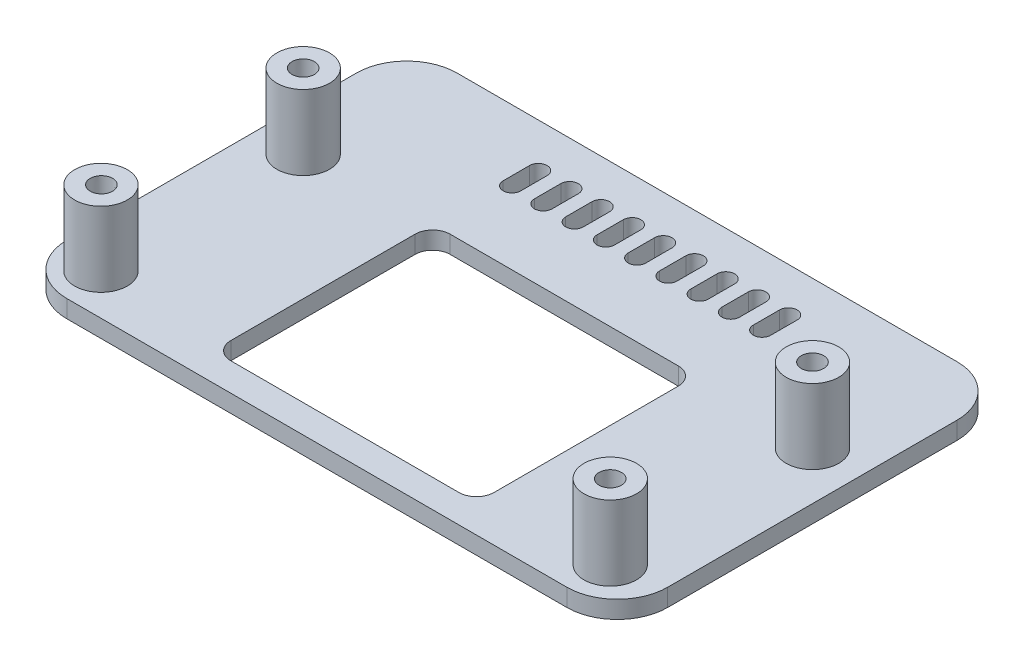
SolidWorks part; units mm, degrees
ref_plane "前视基准面" through (0, 0, 0) normal (0, 0, 1) x (1, 0, 0)
ref_plane "上视基准面" through (0, 0, 0) normal (0, 1, 0) x (1, 0, 0)
ref_plane "右视基准面" through (0, 0, 0) normal (1, 0, 0) x (0, 0, -1)
other "Configuration Table"
sketch "草图1" plane through (0, 0, 0) normal (0, 1, 0) x (1, 0, 0)
  line L1 (-34.4994, 19.3243) -> (34.0006, 19.3243)
  line L2 (-34.4994, 19.3243) -> (-34.4994, -25.1757)
  line L3 (-34.4994, -25.1757) -> (34.0006, -25.1757)
  line L4 (34.0006, 19.3243) -> (34.0006, -25.1757)
  dimension "D1" = 68.5
  dimension "D2" = 44.5
extrude "凸台-拉伸1" add sketch "草图1" along normal blind 2
fillet "圆角1" radius 5.75 4 edges at (34.0006, 1, -19.3243) (34.0006, 1, 25.1757) (-34.4994, 1, 25.1757) (-34.4994, 1, -19.3243)
sketch "草图2" plane through (0, 0, 0) normal (0, -1, 0) x (1, 0, 0)
  line L0 (-28.7494, 25.1757) -> (28.2506, 25.1757) construction
  line L1 (-15.2494, 21.9757) -> (14.7506, 21.9757)
  line L2 (-15.2494, 21.9757) -> (-15.2494, -3.0243)
  line L3 (-15.2494, -3.0243) -> (14.7506, -3.0243)
  line L4 (14.7506, 21.9757) -> (14.7506, -3.0243)
  line L5 (-15.2494, 21.9757) -> (14.7506, -3.0243) construction
  line L6 (-15.2494, -3.0243) -> (14.7506, 21.9757) construction
  point P0 (-0.2494, 9.4757)
  point P8 (-0.2494, 25.1757)
  dimension "D1" = 15.7
  dimension "D2" = 30
  dimension "D3" = 25
extrude "切除-拉伸1" cut sketch "草图2" against normal through all
fillet "圆角2" radius 2 4 edges at (-15.2494, 1, -3.0243) (-15.2494, 1, 21.9757) (14.7506, 1, 21.9757) (14.7506, 1, -3.0243)
sketch "草图3" plane through (0, 2, 0) normal (0, 1, 0) x (1, 0, 0)
  circle A0 centre (-29.5244, 2.5493) radius 3
  circle A1 centre (-29.5244, -20.5007) radius 3
  circle A2 centre (28.5006, -20.4757) radius 3
  circle A3 centre (28.5256, 2.5493) radius 3
  dimension "D1" = 6
extrude "凸台-拉伸2" add sketch "草图3" along normal blind 8.5
sketch "草图4" plane through (0, 10.5, 0) normal (0, 1, 0) x (1, 0, 0)
  circle A0 centre (-29.5244, 2.5493) radius 1.275
  circle A1 centre (-29.4994, -20.4757) radius 1.275
  circle A2 centre (28.5256, -20.5007) radius 1.275
  circle A3 centre (28.5256, 2.5493) radius 1.275
  dimension "D1" = 2.55
extrude "切除-拉伸2" cut sketch "草图4" against normal blind 6 draft 1
sketch "草图5" plane through (0, 0, 0) normal (0, -1, 0) x (1, 0, 0)
  line L0 (-14.4994, -11.3243) -> (-14.4994, -14.3243) construction
  line L1 (-13.4994, -11.3243) -> (-13.4994, -14.3243)
  line L2 (-15.4994, -11.3243) -> (-15.4994, -14.3243)
  line L3 (-10.9369, -11.3243) -> (-10.9369, -14.3243) construction
  line L4 (-9.9369, -11.3243) -> (-9.9369, -14.3243)
  line L5 (-11.9369, -11.3243) -> (-11.9369, -14.3243)
  line L6 (-7.3744, -11.3243) -> (-7.3744, -14.3243) construction
  line L7 (-6.3744, -11.3243) -> (-6.3744, -14.3243)
  line L8 (-8.3744, -11.3243) -> (-8.3744, -14.3243)
  line L9 (-3.8119, -11.3243) -> (-3.8119, -14.3243) construction
  line L10 (-2.8119, -11.3243) -> (-2.8119, -14.3243)
  line L11 (-4.8119, -11.3243) -> (-4.8119, -14.3243)
  line L12 (-0.2494, -11.3243) -> (-0.2494, -14.3243) construction
  line L13 (0.7506, -11.3243) -> (0.7506, -14.3243)
  line L14 (-1.2494, -11.3243) -> (-1.2494, -14.3243)
  line L15 (3.3131, -11.3243) -> (3.3131, -14.3243) construction
  line L16 (4.3131, -11.3243) -> (4.3131, -14.3243)
  line L17 (2.3131, -11.3243) -> (2.3131, -14.3243)
  line L18 (6.8756, -11.3243) -> (6.8756, -14.3243) construction
  line L19 (7.8756, -11.3243) -> (7.8756, -14.3243)
  line L20 (5.8756, -11.3243) -> (5.8756, -14.3243)
  line L21 (10.4381, -11.3243) -> (10.4381, -14.3243) construction
  line L22 (11.4381, -11.3243) -> (11.4381, -14.3243)
  line L23 (9.4381, -11.3243) -> (9.4381, -14.3243)
  line L24 (14.0006, -11.3243) -> (14.0006, -14.3243) construction
  line L25 (15.0006, -11.3243) -> (15.0006, -14.3243)
  line L26 (13.0006, -11.3243) -> (13.0006, -14.3243)
  line L27 (28.2506, -19.3243) -> (-28.7494, -19.3243) construction
  line L28 (-34.4994, -13.5743) -> (-34.4994, 19.4257) construction
  line L29 (34.0006, 19.4257) -> (34.0006, -13.5743) construction
  arc A0 (-13.4994, -11.3243) -> (-15.4994, -11.3243) centre (-14.4994, -11.3243) ccw
  arc A1 (-15.4994, -14.3243) -> (-13.4994, -14.3243) centre (-14.4994, -14.3243) ccw
  arc A2 (-9.9369, -11.3243) -> (-11.9369, -11.3243) centre (-10.9369, -11.3243) ccw
  arc A3 (-11.9369, -14.3243) -> (-9.9369, -14.3243) centre (-10.9369, -14.3243) ccw
  arc A4 (-6.3744, -11.3243) -> (-8.3744, -11.3243) centre (-7.3744, -11.3243) ccw
  arc A5 (-8.3744, -14.3243) -> (-6.3744, -14.3243) centre (-7.3744, -14.3243) ccw
  arc A6 (-2.8119, -11.3243) -> (-4.8119, -11.3243) centre (-3.8119, -11.3243) ccw
  arc A7 (-4.8119, -14.3243) -> (-2.8119, -14.3243) centre (-3.8119, -14.3243) ccw
  arc A8 (0.7506, -11.3243) -> (-1.2494, -11.3243) centre (-0.2494, -11.3243) ccw
  arc A9 (-1.2494, -14.3243) -> (0.7506, -14.3243) centre (-0.2494, -14.3243) ccw
  arc A10 (4.3131, -11.3243) -> (2.3131, -11.3243) centre (3.3131, -11.3243) ccw
  arc A11 (2.3131, -14.3243) -> (4.3131, -14.3243) centre (3.3131, -14.3243) ccw
  arc A12 (7.8756, -11.3243) -> (5.8756, -11.3243) centre (6.8756, -11.3243) ccw
  arc A13 (5.8756, -14.3243) -> (7.8756, -14.3243) centre (6.8756, -14.3243) ccw
  arc A14 (11.4381, -11.3243) -> (9.4381, -11.3243) centre (10.4381, -11.3243) ccw
  arc A15 (9.4381, -14.3243) -> (11.4381, -14.3243) centre (10.4381, -14.3243) ccw
  arc A16 (15.0006, -11.3243) -> (13.0006, -11.3243) centre (14.0006, -11.3243) ccw
  arc A17 (13.0006, -14.3243) -> (15.0006, -14.3243) centre (14.0006, -14.3243) ccw
  point P2 (-14.4994, -12.8243)
  point P7 (0, 0)
  point P10 (-10.9369, -12.8243)
  point P17 (-7.3744, -12.8243)
  point P24 (-3.8119, -12.8243)
  point P31 (-0.2494, -12.8243)
  point P38 (3.3131, -12.8243)
  point P45 (6.8756, -12.8243)
  point P52 (10.4381, -12.8243)
  point P59 (14.0006, -12.8243)
  point P67 (0, 0)
  dimension "D1" = 1
  dimension "D2" = 3
  dimension "D4" = 20
  dimension "D5" = 20
  dimension "D6" = 5
  dimension "D3" = 9
extrude "切除-拉伸3" cut sketch "草图5" against normal blind 10
